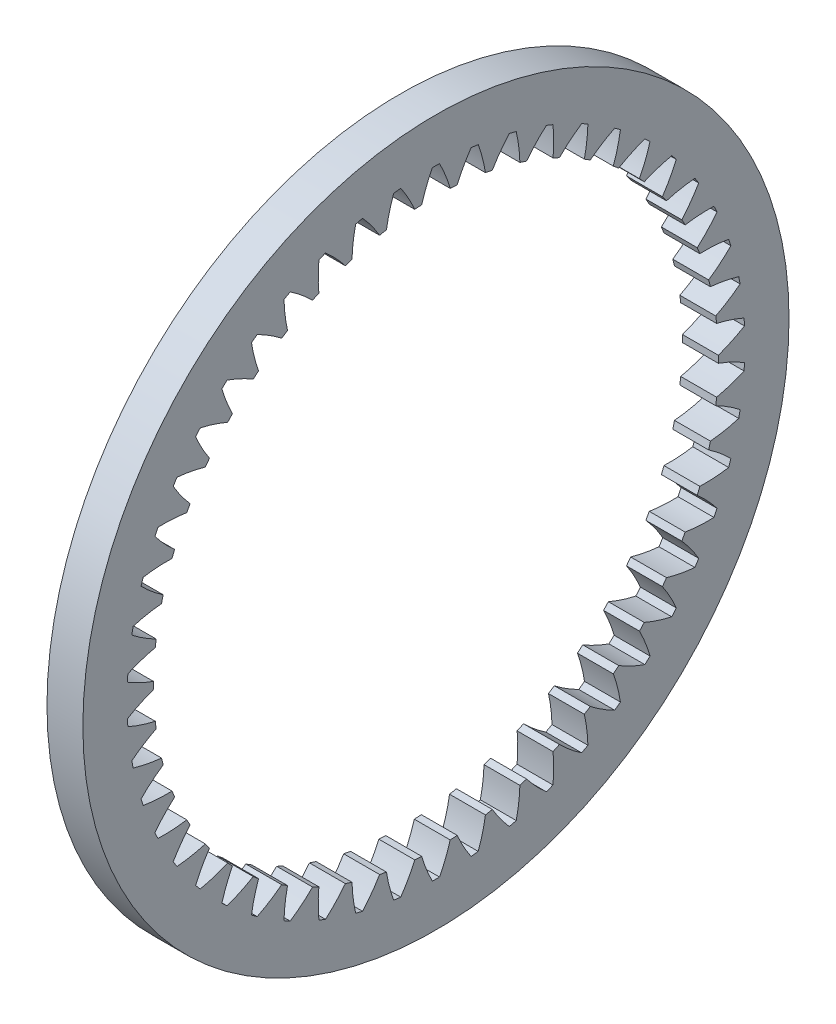
SolidWorks part; units mm, degrees
ref_plane "Plane1" through (0, 0, 0) normal (0, 0, 1) x (1, 0, 0)
ref_plane "Plane2" through (0, 0, 0) normal (0, 1, 0) x (1, 0, 0)
ref_plane "Plane3" through (0, 0, 0) normal (1, 0, 0) x (0, 0, -1)
other "Configuration Table"
sketch "HoldingSke" plane through (0, 0, 0) normal (0, 1, 0) x (1, 0, 0)
  line L0 (0, 0) -> (0.3214, -0.383)
  line L1 (-15, 0) -> (100, 0) construction
  line L2 (0, 0) -> (-2.1039, 2.3779)
  line L3 (0, 0) -> (-11.863, 4.5341)
  line L4 (0, 0) -> (5.5511, 6.6156)
  line L5 (0, 0) -> (-23.7986, -8.8762)
  line L6 (0, 0) -> (-10.5278, -7.1032)
  line L7 (-2.1039, 2.3779) -> (3.3635, 27.1825)
  line L8 (-76.2, 4.3779) -> (-54.61, 4.3779)
  line L9 (-71.009, 38.7566) -> (-53.1078, 45.2721)
  line L10 (-76.2, 71.12) -> (104.1128, 71.12)
  line L11 (0, 0) -> (-6.1, 0)
  line L12 (-76.2, 101.6) -> (-76.133, 101.6)
  line L13 (24.9733, 27.94) -> (52.9518, 28.4284)
  line L14 (24.9733, 27.94) -> (24.9743, 27.94)
  line L15 (24.9733, 27.94) -> (100.4006, 29.5858)
  circle A0 centre (0, 0) radius 60
  circle A1 centre (0, 0) radius 12.7
  circle A2 centre (0, 0) radius 12.7
  dimension "Num_teeth" = 50
  dimension "Pitch_radius" = 180.3128
  dimension "Width" = 6.1
  dimension "Diameter" = 120
sketch "BasProSke" plane through (0, 0, 0) normal (0, 1, 0) x (1, 0, 0)
  line L0 (-10, 0) -> (60, 0) construction
  line L1 (0, 48) -> (0, 60)
  line L2 (0, 48) -> (6.1, 48)
  line L3 (6.1, 48) -> (6.1, 60)
  line L4 (6.1, 60) -> (0, 60)
  dimension "Thickness" = 6.1
  dimension "Diameter" = 120
revolve "Base-Revolve" add sketch "BasProSke" angle 360 about L0
sketch "TooCutSke" plane through (0, 0, 0) normal (1, 0, 0) x (0, 0, -1)
  line L3 (1.738, 49.9698) -> (1.738, 53.6633) construction
  line L4 (0, 0) -> (0, 59.563) construction
  line L5 (0, 0) -> (-4.2903, 68.1927) construction
  line L6 (-21.6015, 41.0107) -> (35.113, 44.5789) construction
  circle A0 centre (0, 0) radius 50 construction
  circle A1 centre (0, 0) radius 52.501 construction
  circle A2 centre (0, 0) radius 42.2862 construction
  circle A3 centre (0, 0) radius 47.9746 construction
  arc A4 (2.4267, 47.9132) -> (0.6033, 52.4975) centre (-21.6015, 41.0107) ccw
  arc A5 (2.4267, 47.9132) -> (-2.4267, 47.9132) centre (0, 0) ccw
  arc A6 (0.6033, 52.4975) -> (-0.6033, 52.4975) centre (0, 0) ccw
  arc A7 (-0.6033, 52.4975) -> (-2.4267, 47.9132) centre (21.6015, 41.0107) ccw
extrude "ToothCut" cut sketch "TooCutSke" along normal through all
fillet "Breaks" [suppressed] radius 0.2
fillet "RootFillets" [suppressed] radius 0.501
pattern_circular "TeethCuts" count 50 every 7.2 about axis through (-10, 0, 0) along (1, 0, 0) of "RootFillets", "Breaks", "ToothCut"
equation "' \"Module@HoldingSke\" = 6.35"
equation "' \"Num_teeth@HoldingSke\" = 24"
equation "' \"Ap@HoldingSke\" =  14.5"
equation "' \"Ap@HoldingSke\" = 14.5"
equation "' \"Width@HoldingSke\" = 12"
equation "' \"Diameter@HoldingSke\" = 8 * 25.4"
equation "' \"Show_teeth@HoldingSke\" = 100"
equation "' \"Backlash@HoldingSke\" = 0.009 * 25.4"
equation "' \"Addendum_fac@HoldingSke\" = 1.0"
equation "' \"Dedendum_fac@HoldingSke\" = 1.25"
equation "' \"Dedendum_add@HoldingSke\" = 0.00005 * 25.4"
equation "' \"Clearance_fac@HoldingSke\" = 0.25"
equation "\"Pitch@HoldingSke\" = 1 / \"Module@HoldingSke\" "
equation "\"Overcut_dia@TooCutSke\" = (\"Num_teeth@HoldingSke\" - 2 * \"Addendum_fac@HoldingSke\") / \"Pitch@HoldingSke\" - 0.002 * 25.4"
equation "\"Pitch_dia@TooCutSke\" = \"Num_teeth@HoldingSke\" / \"Pitch@HoldingSke\""
equation "\"Base_dia@TooCutSke\" = \"Num_teeth@HoldingSke\" / \"Pitch@HoldingSke\" * cos((\"Ap@HoldingSke\"  * 3.14159265 / 180)) * 0.90"
equation "\"Root_dia@TooCutSke\" = \"Num_teeth@HoldingSke\"  / \"Pitch@HoldingSke\" + 2 *  \"Dedendum_fac@HoldingSke\"/ \"Pitch@HoldingSke\" + \"Dedendum_add@HoldingSke\" * 2"
equation "\"Half_ang@TooCutSke\" = 180 / \"Num_teeth@HoldingSke\""
equation "\"Half_CT@TooCutSke\" = \"Num_teeth@HoldingSke\" / \"Pitch@HoldingSke\" * sin((3.14159265 / 2 / \"Num_teeth@HoldingSke\")) / 2 + 10 * \"Backlash@HoldingSke\" / 4"
equation "\"Flank_rad@TooCutSke\" = \"Num_teeth@HoldingSke\" / \"Pitch@HoldingSke\" / 4"
equation "\"Radius@RootFillets\"= \"Clearance_fac@HoldingSke\" / \"Pitch@HoldingSke\" + \"Dedendum_add@HoldingSke\""
equation "\"Break_rad@Breaks\" = 0.02 / \"Pitch@HoldingSke\" * 5"
equation "\"Num_teeth@TeethCuts\" = int( \"Show_teeth@HoldingSke\" ) + 1"
equation "\"Num_teeth@TeethCuts\" = ((sgn( \"Num_teeth@TeethCuts\" - \"Num_teeth@HoldingSke\" )-1)*( \"Num_teeth@TeethCuts\" - \"Num_teeth@HoldingSke\" ))/-2+ \"Num_teeth@HoldingSke\""
equation "\"Num_teeth@TeethCuts\" = ((sgn( \"Num_teeth@TeethCuts\" - 2.0)+1)*( \"Num_teeth@TeethCuts\" - 2.0))/2 +2.0"
equation "\"Angle@TeethCuts\" = 360.0 / \"Num_teeth@HoldingSke\""
equation "\"Diameter@BasProSke\" = \"Num_teeth@HoldingSke\"  / \"Pitch@HoldingSke\" + 2 *  \"Dedendum_fac@HoldingSke\"/ \"Pitch@HoldingSke\" + \"Dedendum_add@HoldingSke\" * 2 + 0.002 * 25.4"
equation "\"Diameter@BasProSke\" = ((sgn( \"Diameter@BasProSke\"  - \"Diameter@HoldingSke\" )+1)*( \"Diameter@BasProSke\"  - \"Diameter@HoldingSke\" ))/2 + \"Diameter@HoldingSke\""
equation "\"Inside_diameter@BasProSke\" =  (\"Num_teeth@HoldingSke\" - 2 * \"Addendum_fac@HoldingSke\") / \"Pitch@HoldingSke\" "
equation "\"Thickness@BasProSke\"  = \"Width@HoldingSke\""
